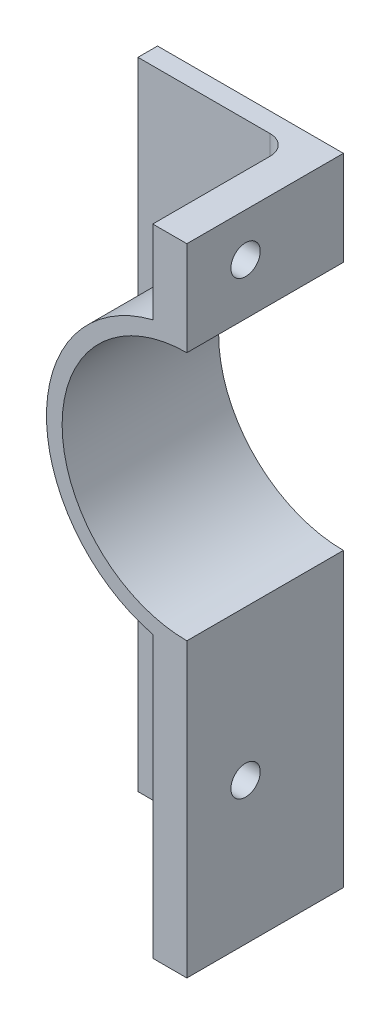
SolidWorks part; units mm, degrees
ref_plane "Front Plane" through (0, 0, 0) normal (0, 0, 1) x (1, 0, 0)
ref_plane "Top Plane" through (0, 0, 0) normal (0, 1, 0) x (1, 0, 0)
ref_plane "Right Plane" through (0, 0, 0) normal (1, 0, 0) x (0, 0, -1)
sketch "Sketch2" plane through (0, 0, 0) normal (0, 0, 1) x (1, 0, 0)
  line L0 (0, 0) -> (0, 82.55)
  line L1 (0, 82.55) -> (50.8, 82.55)
  line L2 (50.8, 82.55) -> (50.8, 0)
  line L3 (50.8, 0) -> (0, 0)
  line L4 (24.13, 82.55) -> (24.13, 0)
  line L7 (19.7022, 82.55) -> (19.7022, 71.7804)
  line L8 (19.7022, 0) -> (19.7022, 36.4236)
  line L9 (28.5578, 82.55) -> (28.5578, 71.7804)
  line L10 (28.5578, 0) -> (28.5578, 36.4236)
  circle A0 centre (24.13, 54.102) radius 16.1925
  arc A1 (19.7022, 71.7804) -> (19.7022, 36.4236) centre (24.13, 54.102) ccw
  arc A2 (28.5578, 36.4236) -> (28.5578, 71.7804) centre (24.13, 54.102) ccw
sketch "Sketch3" plane through (0, 0, 0) normal (1, 0, 0) x (0, 0, -1)
  circle A0 centre (-12.7, 18.4309) radius 1.905
  circle A1 centre (-12.7, 76.9461) radius 1.905
extrude "Boss-Extrude5" add sketch "Sketch2" along normal blind 20.32 contours L7 A1 L8 L3 L4 A0 L1 region at (20.5476, 18.2118, 0)
extrude "Boss-Extrude6" add sketch "Sketch2<7>" along normal blind 2.54 contours A1 L7 L1 L0 L3 L8 region at (8.6771, 37.6036, 0)
sketch "Sketch2<7>" plane through (0, 0, 0) normal (0, 0, 1) x (1, 0, 0) same geometry as "Sketch2"
extrude "Cut-Extrude3" cut sketch "Sketch3" along normal through all both
fillet "Fillet3" radius 2.54 3 edges at (19.7022, 77.1652, 2.54) (5.9055, 54.102, 2.54) (19.7022, 18.2118, 2.54)
